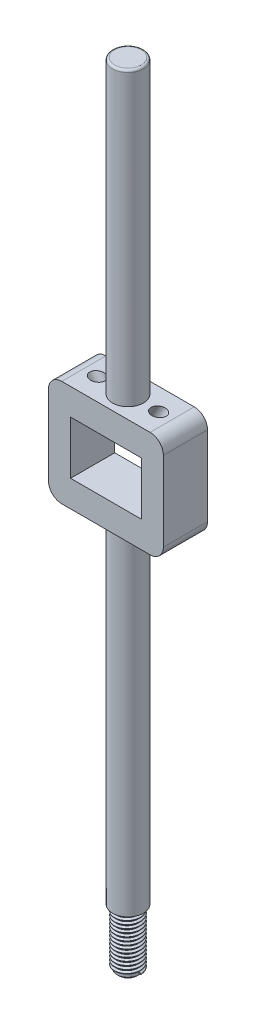
SolidWorks part; units mm, degrees
material "AISI 304"
ref_plane "Front Plane" through (0, 0, 0) normal (0, 0, 1) x (1, 0, 0)
ref_plane "Top Plane" through (0, 0, 0) normal (0, 1, 0) x (1, 0, 0)
ref_plane "Right Plane" through (0, 0, 0) normal (1, 0, 0) x (0, 0, -1)
sketch "Sketch1" plane through (0, 0, 0) normal (0, 0, 1) x (1, 0, 0)
  line L1 (0, 0) -> (6, 0)
  line L2 (0, 0) -> (0, 6)
  line L5 (6, 6) -> (-10, 6)
  line L6 (6, 6) -> (6, -6)
  line L7 (6, -6) -> (-10, -6)
  line L8 (-10, 6) -> (-10, -6)
  line L9 (-12, 12) -> (8, 12)
  line L10 (-15, 9) -> (-15, -9)
  line L11 (-12, -12) -> (8, -12)
  line L12 (11, 9) -> (11, -9)
  arc A0 (8, 12) -> (11, 9) centre (8, 9) cw
  arc A1 (11, -9) -> (8, -12) centre (8, -9) cw
  arc A2 (-12, -12) -> (-15, -9) centre (-12, -9) cw
  arc A3 (-15, 9) -> (-12, 12) centre (-12, 9) cw
  dimension "D9" = 3
  dimension "D1" = 6
  dimension "D2" = 6
  dimension "D3" = 12
  dimension "D4" = 16
  dimension "D6" = 5
  dimension "D7" = 6
  dimension "D8" = 6
extrude "Boss-Extrude1" add sketch "Sketch1" along normal blind 5 and the other way blind 5 contours A3 L10 A2 L11 A1 L12 A0 L9 L8 L5 L6 L7 region at (-2, 11.6462, 0)
sketch "Sketch3" plane through (0, 12, 0) normal (0, 1, 0) x (1, 0, 0)
  line L0 (-13.2, 0) -> (13.2, 0) construction
  line L1 (8, 5) -> (8, -5) construction
  circle A0 centre (-2, 0) radius 3.5
  dimension "D1" = 10
extrude "Boss-Extrude2" add sketch "Sketch3" along normal blind 66
fillet "Fillet1" radius 0.5 1 edges at (-2, 78, 3.5)
sketch "Sketch4" plane through (0, 0, 0) normal (0, 0, 1) x (1, 0, 0)
  line L0 (1.5, 12) -> (1.5, 22)
  line L1 (1.5, 12) -> (1.5, 77.5) construction
  line L2 (10.502, 21.6542) -> (-2, 0)
  line L4 (10.502, 21.6542) -> (23.7287, 14.0178) construction
  point P7 (-2, 0)
  dimension "D1" = 10
  dimension "D2" = 30
ref_plane "Plane1" through (12.002, 20.7882, 0) normal (-0.5, -0.866, 0) x (0.866, -0.5, 0)
sketch "Sketch5" plane through (12.002, 20.7882, 0) normal (-0.5, -0.866, 0) x (0.866, -0.5, 0)
  line L0 (-1.7321, 0) -> (13.5408, 0) construction
  circle A0 centre (-1.7321, 0) radius 1.5
extrude "Cut-Extrude1" cut sketch "Sketch5" against normal through all and the other way blind 25
sketch "Sketch6" plane through (0, 0, 0) normal (0, 0, 1) x (1, 0, 0)
  line L0 (-5.5, 16.0248) -> (-5.5, 12)
  line L3 (-2, 0) -> (-13.2008, 19.4003) construction
  line L4 (-13.2008, 19.4003) -> (-10.9729, 20.6866) construction
  line L5 (-5.5, 77.5) -> (-5.5, 12) construction
  point P0 (-2, 0)
  dimension "D1" = 30
ref_plane "Plane2" through (-11.7008, 20.2663, 0) normal (0.5, -0.866, 0) x (0.866, 0.5, 0)
sketch "Sketch7" plane through (-11.7008, 20.2663, 0) normal (0.5, -0.866, 0) x (0.866, 0.5, 0)
  circle A0 centre (-1.7321, 0) radius 1.5
extrude "Cut-Extrude2" cut sketch "Sketch7" against normal through all and the other way blind 23
sketch "Sketch8" plane through (0, -12, 0) normal (0, -1, 0) x (1, 0, 0)
  circle A0 centre (-2, 0) radius 3.5
extrude "Boss-Extrude3" add sketch "Sketch8" along normal blind 76
sketch "Sketch9" plane through (0, -88, 0) normal (0, -1, 0) x (1, 0, 0)
  circle A0 centre (-2, 0) radius 2.5
extrude "Boss-Extrude4" add sketch "Sketch9" along normal blind 13
chamfer "Chamfer1" distance 0.45 angle 45 1 edges at (-2, -101, -2.5)
thread "Thread1" pitch 0.8 method extrude profile "Thread Profile1" start angle 0, offset 0, length 0, pitch 0.8, diameter 5
ref_plane "Plane3" through (0.5, -100.55, 0) normal (0, 0, 1) x (1, 0, 0)
sketch "Thread Profile1" plane through (0.5, -100.55, 0) normal (0, 0, 1) x (1, 0, 0)
  line L0 (0, 0) -> (0, 0.8) construction
  line L1 (0, 0) -> (0.433, 0.25)
  line L2 (0.433, 0.25) -> (0.433, 0.35)
  line L3 (0.433, 0.35) -> (0, 0.6)
  line L4 (0.433, 0.3) -> (0, 0.3) construction
  line L11 (0, 0) -> (0, 0.6)
  point P2 (0, 0)
  dimension "Pitch" = 0.8
  dimension "Profile_Angle" = 60
  dimension "Profile_Land" = 0.1
  dimension "Profile_Height" = 0.433
